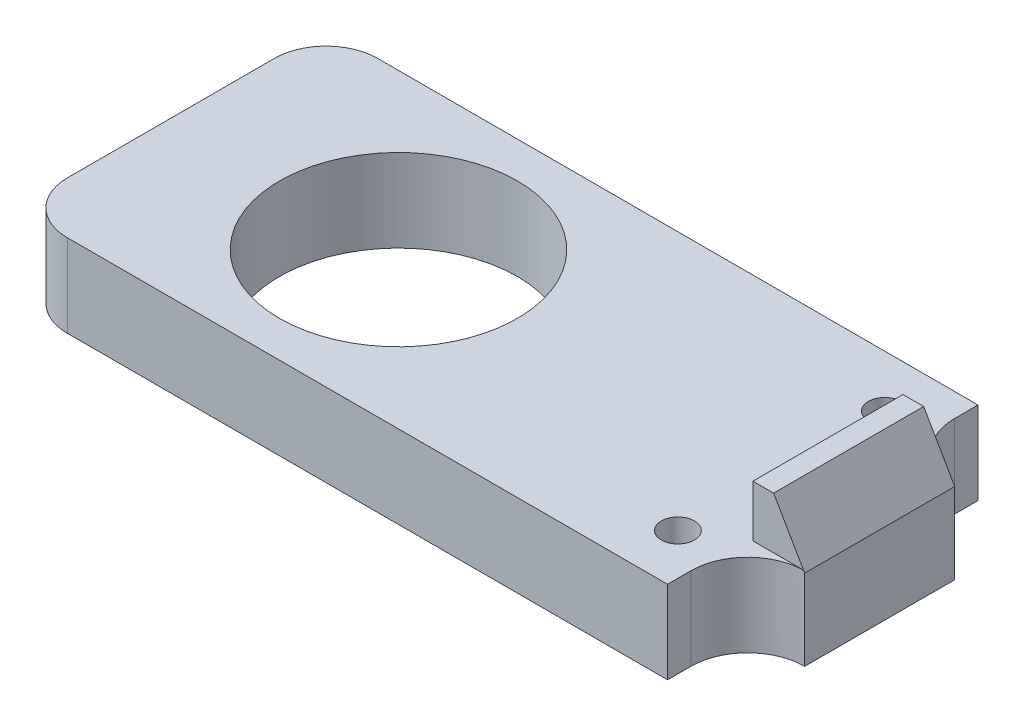
SolidWorks part; units mm, degrees
ref_plane "Front Plane" through (0, 0, 0) normal (0, 0, 1) x (1, 0, 0)
ref_plane "Top Plane" through (0, 0, 0) normal (0, 1, 0) x (1, 0, 0)
ref_plane "Right Plane" through (0, 0, 0) normal (1, 0, 0) x (0, 0, -1)
sketch "Sketch1" plane through (0, 0, 0) normal (0, 1, 0) x (1, 0, 0)
  line L1 (0, 0) -> (63, 0)
  line L2 (0, 0) -> (0, 30)
  line L3 (0, 30) -> (63, 30)
  line L4 (63, 0) -> (63, 30)
  circle A0 centre (22, 15) radius 11.5
  point P7 (0, 15)
  dimension "D3" = 23
  dimension "D4" = 22
  dimension "D1" = 63
  dimension "D2" = 30
extrude "Boss-Extrude1" add sketch "Sketch1" along normal blind 5
sketch "Sketch2" plane through (0, 5, 0) normal (0, 1, 0) x (1, 0, 0)
  line L0 (63, 0) -> (63, 30) construction
  line L1 (0, 0) -> (63, 0) construction
  line L2 (63, 30) -> (0, 30) construction
  circle A0 centre (59, 25) radius 1.6
  circle A1 centre (59, 5) radius 1.6
  dimension "D1" = 3.2
  dimension "D4" = 5
  dimension "D2" = 4
  dimension "D3" = 5
extrude "Cut-Extrude1" cut sketch "Sketch2" against normal through all
fillet "Fillet1" radius 5 2 edges at (0, 2.5, 0) (0, 2.5, -30)
sketch "Sketch3" plane through (63, 0, 0) normal (1, 0, 0) x (0, 0, -1)
  line L1 (7.75, 0) -> (22.25, 0)
  line L2 (7.75, 0) -> (7.75, 5)
  line L3 (7.75, 5) -> (22.25, 5)
  line L4 (22.25, 0) -> (22.25, 5)
  line L5 (0, 5) -> (30, 5) construction
  line L6 (0, 0) -> (30, 0) construction
  point P4 (15, 0)
  point P8 (15, 0)
  dimension "D1" = 14.5
extrude "Boss-Extrude2" add sketch "Sketch3" along normal blind 0.5 contours L2 L3 L4 L1
sketch "Sketch4" plane through (63.5, 0, 0) normal (1, 0, 0) x (0, 0, -1)
  line L0 (22.25, 0) -> (22.25, 5) construction
  line L1 (7.75, 0) -> (22.25, 0)
  line L2 (7.75, 0) -> (7.75, 10)
  line L3 (7.75, 10) -> (22.25, 10)
  line L4 (22.25, 0) -> (22.25, 10)
  dimension "D1" = 10
extrude "Boss-Extrude3" add sketch "Sketch4" along normal blind 5
fillet "Fillet2" radius 5.5 2 edges at (63, 2.5, -7.75) (63, 2.5, -22.25)
sketch "Sketch5" plane through (68.5, 0, 0) normal (1, 0, 0) x (0, 0, -1)
  line L0 (7.75, 10) -> (7.75, 0) construction
  line L1 (4.5413, 5) -> (7.75, 5)
  line L2 (4.5413, 5) -> (4.5413, 10)
  line L3 (4.5413, 10) -> (7.75, 10)
  line L4 (7.75, 5) -> (7.75, 10)
  line L5 (22.25, 10) -> (25.4587, 10)
  line L6 (22.25, 10) -> (22.25, 5)
  line L7 (22.25, 5) -> (25.4587, 5)
  line L8 (25.4587, 10) -> (25.4587, 5)
  line L9 (22.25, 0) -> (22.25, 10) construction
extrude "Cut-Extrude2" cut sketch "Sketch5" against normal through all
chamfer "Chamfer1" distance 3 angle 60 1 edges at (68.5, 10, -15) first distance on face at (66, 10, -15)
sketch "Sketch6" plane through (0, 0, 0) normal (0, -1, 0) x (1, 0, 0)
  line L12 (63, 0) -> (5, 0)
  line L13 (0, -5) -> (0, -25)
  line L14 (5, -30) -> (63, -30)
  line L15 (63, -30) -> (63, -27.75)
  line L16 (68.5, -22.25) -> (68.5, -7.75)
  line L17 (63, -2.25) -> (63, 0)
  line L18 (63, 0) -> (5, 0)
  line L19 (0, -5) -> (0, -25)
  line L20 (5, -30) -> (63, -30)
  line L21 (63, -30) -> (63, -27.75)
  line L22 (68.5, -22.25) -> (68.5, -7.75)
  line L23 (63, -2.25) -> (63, 0)
  arc A8 (5, 0) -> (0, -5) centre (5, -5) ccw
  arc A9 (0, -25) -> (5, -30) centre (5, -25) ccw
  arc A10 (68.5, -22.25) -> (63, -27.75) centre (68.5, -27.75) ccw
  arc A11 (63, -2.25) -> (68.5, -7.75) centre (68.5, -2.25) ccw
  arc A12 (5, 0) -> (0, -5) centre (5, -5) ccw
  arc A13 (0, -25) -> (5, -30) centre (5, -25) ccw
  arc A14 (68.5, -22.25) -> (63, -27.75) centre (68.5, -27.75) ccw
  arc A15 (63, -2.25) -> (68.5, -7.75) centre (68.5, -2.25) ccw
  circle M11 centre (59, -25) radius 1.6
  circle M12 centre (59, -5) radius 1.6
  line M13 (63, 0) -> (5, 0)
  arc M14 (5, 0) -> (0, -5) centre (5, -5) ccw
  line M15 (0, -5) -> (0, -25)
  arc M16 (0, -25) -> (5, -30) centre (5, -25) ccw
  line M17 (5, -30) -> (63, -30)
  line M18 (63, -30) -> (63, -27.75)
  arc M19 (63, -27.75) -> (68.5, -22.25) centre (68.5, -27.75) cw
  line M20 (68.5, -22.25) -> (68.5, -7.75)
  arc M21 (68.5, -7.75) -> (63, -2.25) centre (68.5, -2.25) cw
  line M22 (63, -2.25) -> (63, 0)
  circle M23 centre (22, -15) radius 11.5
  dimension "D1" = 0
extrude "Boss-Extrude4" add sketch "Sketch6" along normal blind 3 contours M22 M13 M14 M15 M16 M17 M18 M19 M20 M21 M12 M23 M11 region at (36.0357, 0, -15)
